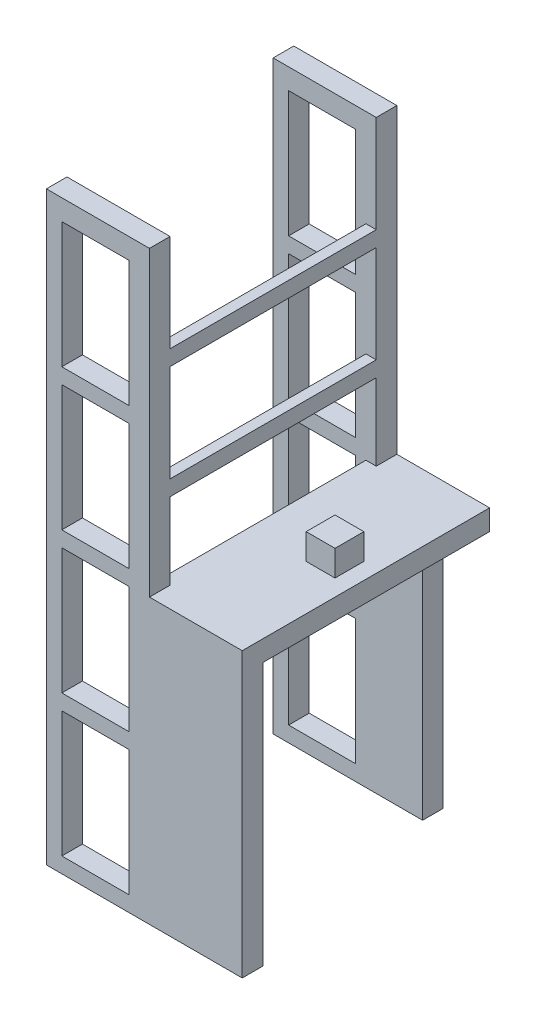
SolidWorks part; units mm, degrees
ref_plane "前视基准面" through (0, 0, 0) normal (0, 0, 1) x (1, 0, 0)
ref_plane "上视基准面" through (0, 0, 0) normal (0, 1, 0) x (1, 0, 0)
ref_plane "右视基准面" through (0, 0, 0) normal (1, 0, 0) x (0, 0, -1)
other "Configuration Table"
sketch "草图1" plane through (0, 0, 0) normal (0, 1, 0) x (1, 0, 0)
  line L1 (-1.4, -1.4) -> (1.4, -1.4)
  line L2 (-1.4, -1.4) -> (-1.4, 1.4)
  line L3 (-1.4, 1.4) -> (1.4, 1.4)
  line L4 (1.4, -1.4) -> (1.4, 1.4)
  line L5 (-1.4, -1.4) -> (1.4, 1.4) construction
  line L6 (-1.4, 1.4) -> (1.4, -1.4) construction
  point P0 (0, 0)
  dimension "D1" = 2.8
  dimension "D2" = 2.8
extrude "凸台-拉伸1" add sketch "草图1" along normal blind 4.5 contours L3 L4 L1 L2
sketch "草图2" plane through (0, 0, 0) normal (0, -1, 0) x (1, 0, 0)
  line L1 (3, 12) -> (-6, 12)
  line L2 (3, 12) -> (3, -12)
  line L3 (3, -12) -> (-6, -12)
  line L4 (-6, 12) -> (-6, -12)
  dimension "D1" = 12
  dimension "D2" = 12
  dimension "D3" = 3
  dimension "D4" = 6
extrude "凸台-拉伸2" add sketch "草图2" against normal blind 2
sketch "草图3" plane through (-6, 0, 0) normal (-1, 0, 0) x (0, 0, 1)
  line L0 (12, 0) -> (-12, 0) construction
  line L1 (12, 0) -> (-12, 0)
  line L2 (12, 0) -> (12, 31.3)
  line L3 (12, 31.3) -> (-12, 31.3)
  line L4 (-12, 0) -> (-12, 31.3)
  line L5 (-12, 2) -> (-12, 0) construction
  line L6 (12, 2) -> (12, 0) construction
  line L7 (0, 0) -> (0, 9.4333) construction
  line L8 (12, 9.4333) -> (-12, 9.4333)
  line L9 (12, 9.4333) -> (12, 10.9333)
  line L10 (12, 10.9333) -> (-12, 10.9333)
  line L11 (-12, 9.4333) -> (-12, 10.9333)
  line L12 (12, 20.3667) -> (-12, 20.3667)
  line L13 (12, 20.3667) -> (12, 21.8667)
  line L14 (12, 21.8667) -> (-12, 21.8667)
  line L15 (-12, 20.3667) -> (-12, 21.8667)
  line L16 (0, 10.9333) -> (0, 20.3667) construction
  line L17 (0, 21.8667) -> (0, 31.3) construction
  line L18 (-10, 31.3) -> (-10, 0)
  line L19 (10, 31.3) -> (10, 0)
  line M16 (-12, 0) -> (12, 0)
  line M17 (12, 0) -> (12, 2)
  line M18 (12, 2) -> (-12, 2)
  line M19 (-12, 2) -> (-12, 0)
  dimension "D1" = 31.3
  dimension "D2" = 1.5
  dimension "D3" = 1.5
  dimension "D4" = 2
  dimension "D5" = 2
extrude "凸台-拉伸3" add sketch "草图3" along normal blind 1 contours L2 L3 L4 L1
extrude "切除-拉伸1" cut sketch "草图3<3>" along normal through all contours L19 L8 L18 M18 | L19 L12 L18 L10 | L19 L3 L18 L14 region at (-6, 5.7167, 0) region at (-6, 15.65, 0) region at (-6, 26.5833, 0)
sketch "草图3<3>" plane through (-6, 0, 0) normal (-1, 0, 0) x (0, 0, 1) same geometry as "草图3"
extrude "凸台-拉伸4" add sketch "草图3<4>" along normal blind 10 contours L8 L19 L2 M18 | L10 L19 L8 L2 | L12 L19 L10 L2 | L14 L19 L12 L2 | L3 L19 L14 L2 | L18 L3 L4 L14 | L18 L14 L4 L12 | L18 L12 L4 L10 | L18 L10 L4 L8 | L18 L8 L4 M18 | L19 M18 M16 M17 | L18 M18 M19 M16 region at (-6, 1, 11) region at (-6, 5.7167, 11) region at (-6, 1, -11) region at (-6, 10.1833, 11) region at (-6, 5.7167, -11) region at (-6, 15.65, 11) region at (-6, 10.1833, -11) region at (-6, 21.1167, 11) region at (-6, 15.65, -11) region at (-6, 26.5833, 11) region at (-6, 21.1167, -11) region at (-6, 26.5833, -11)
sketch "草图3<4>" plane through (-6, 0, 0) normal (-1, 0, 0) x (0, 0, 1) same geometry as "草图3"
sketch "草图5" plane through (0, 0, 0) normal (0, -1, 0) x (1, 0, 0)
  line L0 (-16, 10) -> (-16, 12) construction
  line L1 (-16, 12) -> (3, 12)
  line L2 (-16, 12) -> (-16, 10)
  line L3 (-16, 10) -> (3, 10)
  line L4 (3, 12) -> (3, 10)
  line L5 (3, 12) -> (-16, 12) construction
  line L6 (-16, -10) -> (-7, -10) construction
  line L7 (-16, -10) -> (-1.5, -10)
  line L8 (-16, -10) -> (-16, -12)
  line L9 (-16, -12) -> (-1.5, -12)
  line L10 (-1.5, -10) -> (-1.5, -12)
  line L11 (-16, -12) -> (3, -12) construction
  line L12 (-16, 10) -> (-7, 10) construction
  line L13 (3, -12) -> (3, 12) construction
  point P16 (-14.2445, -10)
  point P18 (-16, 8.7346)
  point P21 (0, 0)
  dimension "D1" = 14.5
extrude "凸台-拉伸5" add sketch "草图5" along normal blind 25.5 contours L3 L4 L1 L2 | L9 L10 L7 L8
sketch "草图6" plane through (0, 0, -12) normal (0, 0, -1) x (-1, 0, 0)
  line L0 (16, -25.5) -> (1.5, -25.5) construction
  line L1 (14.5, -24) -> (8, -24)
  line L2 (14.5, -24) -> (14.5, 29.3)
  line L3 (14.5, 29.3) -> (8, 29.3)
  line L4 (8, -24) -> (8, 29.3)
  line L5 (16, -25.5) -> (16, 31.3) construction
  line L6 (16, 31.3) -> (6, 31.3) construction
  line L7 (6, 2) -> (6, 31.3) construction
  line L8 (8, -11.8) -> (14.5, -11.8)
  line L9 (8, -10.3) -> (14.5, -10.3)
  line L10 (8, 15.6) -> (14.5, 15.6)
  line L11 (8, 17.1) -> (14.5, 17.1)
  line L12 (8, 1.9) -> (14.5, 1.9)
  line L13 (8, 3.4) -> (14.5, 3.4)
  line L14 (11.25, -24) -> (11.25, -11.8) construction
  line L15 (11.25, -10.3) -> (11.25, 1.9) construction
  line L16 (11.25, 3.4) -> (11.25, 15.6) construction
  line L17 (11.25, 17.1) -> (11.25, 29.3) construction
  dimension "D1" = 1.5
  dimension "D2" = 1.5
  dimension "D3" = 2
  dimension "D4" = 2
  dimension "D5" = 1.5
  dimension "D6" = 1.5
  dimension "D7" = 1.5
extrude "切除-拉伸2" cut sketch "草图6" against normal through all contours L8 L4 L1 L2 | L12 L4 L9 L2 | L4 L13 L2 L10 | L4 L11 L2 L3 region at (-11.25, -17.9, -12) region at (-11.25, -4.2, -12) region at (-11.25, 9.5, -12) region at (-11.25, 23.2, -12)
